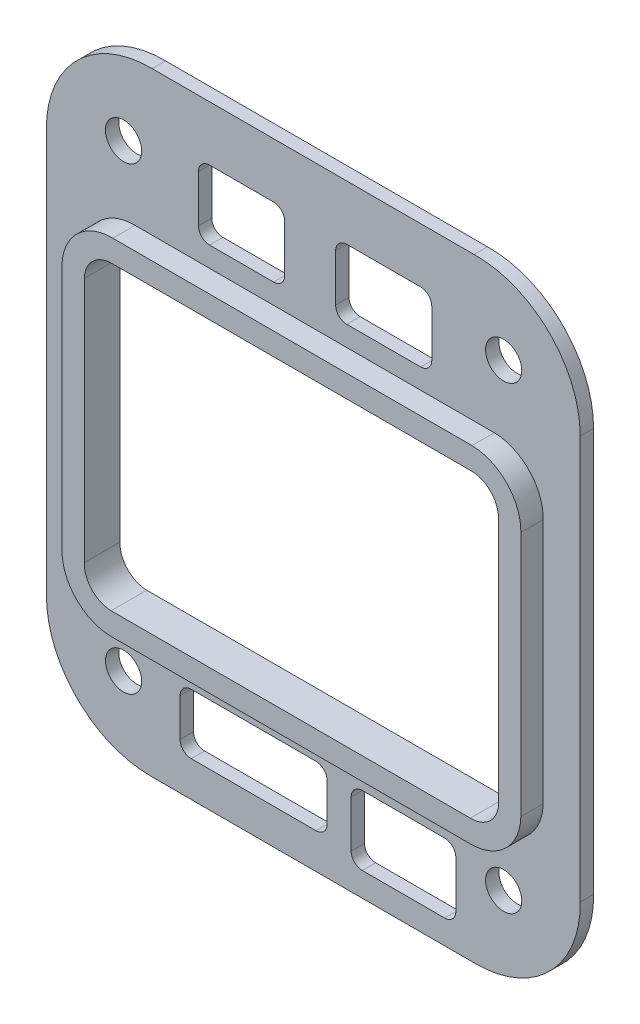
SolidWorks part; units mm, degrees
ref_plane "前视基准面" through (0, 0, 0) normal (0, 0, 1) x (1, 0, 0)
ref_plane "上视基准面" through (0, 0, 0) normal (0, 1, 0) x (1, 0, 0)
ref_plane "右视基准面" through (0, 0, 0) normal (1, 0, 0) x (0, 0, -1)
sketch "Model" plane through (0, 0, 0) normal (0, 0, 1) x (1, 0, 0)
  line L0 (134.239, 61.595) -> (134.239, 83.6932)
  line L1 (99.441, 59.182) -> (131.699, 59.182)
  line L2 (99.568, 86.233) -> (131.826, 86.233)
  line L3 (97.028, 61.722) -> (97.028, 83.82)
  line L4 (103.632, 50.276) -> (103.632, 53.6735)
  line L5 (104.632, 49.276) -> (115.84, 49.276)
  line L6 (116.84, 50.276) -> (116.84, 53.6735)
  line L7 (104.632, 54.6735) -> (115.84, 54.6735)
  line L8 (118.999, 49.26) -> (118.999, 53.483)
  line L9 (119.999, 48.26) -> (127.397, 48.26)
  line L10 (128.397, 49.26) -> (128.397, 53.483)
  line L11 (119.999, 54.483) -> (127.397, 54.483)
  line L12 (118.602, 96.266) -> (125.238, 96.266)
  line L13 (126.238, 91.043) -> (126.238, 95.266)
  line L14 (118.602, 90.043) -> (125.238, 90.043)
  line L15 (117.602, 91.043) -> (117.602, 95.266)
  line L16 (105.283, 91.043) -> (105.283, 95.266)
  line L17 (106.283, 90.043) -> (112.03, 90.043)
  line L18 (113.03, 91.043) -> (113.03, 95.266)
  line L19 (106.283, 96.266) -> (112.03, 96.266)
  line L20 (91.6287, 55.4633) -> (91.6287, 91.6983)
  line L21 (100.9948, 46.0972) -> (130.2038, 46.0972)
  line L22 (139.5708, 55.5903) -> (139.5708, 91.836)
  line L23 (101.1218, 101.1915) -> (130.0388, 101.1915)
  line L24 (95.028, 61.7439) -> (95.028, 83.8419)
  line L25 (99.5899, 88.233) -> (131.8479, 88.233)
  line L26 (136.239, 61.5731) -> (136.239, 83.6714)
  line L27 (99.4191, 57.182) -> (131.6771, 57.182)
  arc A0 (99.568, 86.233) -> (97.028, 83.82) centre (99.5045, 83.7565) ccw
  arc A1 (134.239, 83.6932) -> (131.826, 86.233) centre (131.7625, 83.7565) ccw
  arc A2 (97.028, 61.722) -> (99.441, 59.182) centre (99.5045, 61.6585) ccw
  arc A3 (131.699, 59.182) -> (134.239, 61.595) centre (131.7625, 61.6585) ccw
  circle A4 centre (98.5564, 94.2998) radius 1.626
  arc A5 (101.1218, 101.1915) -> (91.6287, 91.6983) centre (100.9948, 91.8253) ccw
  circle A6 centre (132.694, 53.0502) radius 1.626
  circle A7 centre (132.694, 94.2998) radius 1.626
  circle A8 centre (98.5564, 53.0502) radius 1.626
  arc A9 (91.6287, 55.4633) -> (100.9948, 46.0972) centre (100.9947, 55.4632) ccw
  arc A10 (139.5708, 91.836) -> (130.0388, 101.1915) centre (130.2048, 91.8269) ccw
  arc A11 (130.2038, 46.0972) -> (139.5708, 55.5903) centre (130.2046, 55.4642) ccw
  arc A12 (118.999, 49.26) -> (119.999, 48.26) centre (119.999, 49.26) ccw
  arc A13 (127.397, 48.26) -> (128.397, 49.26) centre (127.397, 49.26) ccw
  arc A14 (128.397, 53.483) -> (127.397, 54.483) centre (127.397, 53.483) ccw
  arc A15 (119.999, 54.483) -> (118.999, 53.483) centre (119.999, 53.483) ccw
  arc A16 (103.632, 50.276) -> (104.632, 49.276) centre (104.632, 50.276) ccw
  arc A17 (115.84, 49.276) -> (116.84, 50.276) centre (115.84, 50.276) ccw
  arc A18 (116.84, 53.6735) -> (115.84, 54.6735) centre (115.84, 53.6735) ccw
  arc A19 (104.632, 54.6735) -> (103.632, 53.6735) centre (104.632, 53.6735) ccw
  arc A20 (125.238, 90.043) -> (126.238, 91.043) centre (125.238, 91.043) ccw
  arc A21 (126.238, 95.266) -> (125.238, 96.266) centre (125.238, 95.266) ccw
  arc A22 (118.602, 90.043) -> (117.602, 91.043) centre (118.602, 91.043) cw
  arc A23 (117.602, 95.266) -> (118.602, 96.266) centre (118.602, 95.266) cw
  arc A24 (106.283, 90.043) -> (105.283, 91.043) centre (106.283, 91.043) cw
  arc A25 (113.03, 91.043) -> (112.03, 90.043) centre (112.03, 91.043) cw
  arc A26 (113.03, 95.266) -> (112.03, 96.266) centre (112.03, 95.266) ccw
  arc A27 (106.283, 96.266) -> (105.283, 95.266) centre (106.283, 95.266) ccw
  arc A28 (99.5899, 88.233) -> (95.028, 83.8419) centre (99.5045, 83.7565) ccw
  arc A29 (136.239, 83.6714) -> (131.8479, 88.233) centre (131.7625, 83.7565) ccw
  arc A30 (131.6771, 57.182) -> (136.239, 61.5731) centre (131.7625, 61.6585) ccw
  arc A31 (95.028, 61.7439) -> (99.4191, 57.182) centre (99.5045, 61.6585) ccw
  dimension "D1" = 1
  dimension "D2" = 2
extrude "凸台-拉伸1" add sketch "Model" along normal blind 1.2 contours L21 A11 L22 A10 L23 A5 L20 A9 A31 L24 A28 L25 A29 L26 A30 L27 A27 L19 A26 L18 A25 L17 A24 L16 A19 L7 A18 L6 A17 L5 A16 L4 A15 L11 A14 L10 A13 L9 A12 L8 A4 A6 A7 region at (92.359, 73.5808, 0)
extrude "凸台-拉伸2" add sketch "Model<4>" along normal blind 3.2 contours L24 A31 L27 A30 L26 A29 L25 A28 A3 L1 A2 L3 A0 L2 A1 L0 region at (95.544, 72.7929, 0)
sketch "Model<4>" plane through (0, 0, 0) normal (0, 0, 1) x (1, 0, 0) same geometry as "Model"
